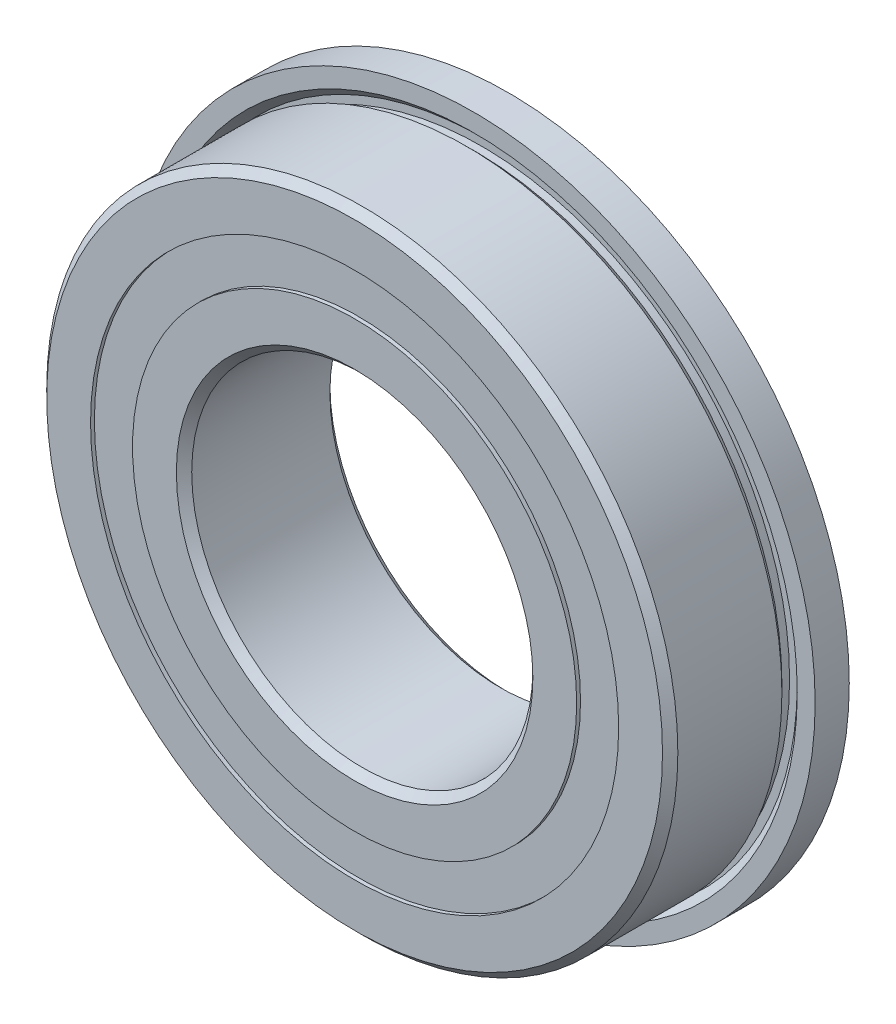
SolidWorks part; units mm, degrees
ref_plane "Front Plane" through (0, 0, 0) normal (0, 0, 1) x (1, 0, 0)
ref_plane "Top Plane" through (0, 0, 0) normal (0, 1, 0) x (1, 0, 0)
ref_plane "Right Plane" through (0, 0, 0) normal (1, 0, 0) x (0, 0, -1)
sketch "Sketch1" plane through (0, 0, 0) normal (0, 0, 1) x (1, 0, 0)
  circle A0 centre (0, 0) radius 10
  dimension "ID" = 20
sketch "Sketch2" plane through (0, 0, 0) normal (1, 0, 0) x (0, 0, -1)
  line L0 (-4.5, 0) -> (4.5, 0) construction
  line L1 (0, 18.5) -> (0, -18.5) construction
  line L2 (4.05, 18.5) -> (-4.05, 18.5) construction
  line L3 (-4.05, 18.5) -> (-4.5, 18.05)
  line L4 (-4.5, 18.05) -> (-4.5, 15.4808)
  line L5 (-4.5, 15.4808) -> (-2, 15.4808)
  line L6 (4.5, 15.4808) -> (2, 15.4808)
  line L7 (4.5, 18.05) -> (4.5, 15.4808)
  line L8 (4.05, 18.5) -> (4.5, 18.05) construction
  line L9 (0, 18.5) -> (0, 14.25) construction
  line L10 (0, 14.25) -> (0, 10) construction
  line L11 (2.5, 0) -> (2.5, 18.5) construction
  line L12 (4.5, 18.05) -> (4.5, 20)
  line L13 (4.5, 20) -> (2.5, 20)
  line L14 (2.5, 20) -> (2.5, 18.95)
  line L15 (2.5, 18.95) -> (2.95, 18.5)
  line L16 (2.95, 18.5) -> (2.95, 18.05)
  line L17 (2.95, 18.05) -> (2.5, 18.05)
  line L18 (2.5, 18.05) -> (2.05, 18.5)
  line L19 (-4.05, 18.5) -> (2.05, 18.5)
  line L20 (4.5, 20) -> (4.5, -20) construction
  line L21 (2.5, 18.5) -> (2.5, 18.95) construction
  line L22 (2.5, 18.5) -> (2.05, 18.5) construction
  line L23 (0, 10) -> (0, -10) construction
  arc A0 (-2, 15.4808) -> (2, 15.4808) centre (0, 14.25) cw
  point P14 (0, 10)
  point P15 (2.5, 0)
  point P25 (4.5, 0)
  point P29 (-4.05, -18.5)
  dimension "D1" = 45
  dimension "D2" = 0.45
  dimension "D3" = 4
  dimension "D4" = 1.2308
  dimension "Flange Thickness" = 2
  dimension "Flange OD" = 40
  dimension "Width" = 9
  dimension "OD" = 37
sketch "Sketch7" plane through (0, 0, 0) normal (1, 0, 0) x (0, 0, -1)
  line L13 (4.5, 20) -> (2.5, 20)
  line L14 (2.5, 20) -> (2.5, 18.95)
  line L15 (2.5, 18.95) -> (2.95, 18.5)
  line L16 (2.95, 18.5) -> (2.95, 18.05)
  line L17 (2.95, 18.05) -> (2.5, 18.05)
  line L18 (2.5, 18.05) -> (2.05, 18.5)
  line L19 (2.05, 18.5) -> (-4.05, 18.5)
  line L20 (-4.05, 18.5) -> (-4.5, 18.05)
  line L21 (-4.5, 18.05) -> (-4.5, 15.4808)
  line L22 (-4.5, 15.4808) -> (-2, 15.4808)
  line L23 (2, 15.4808) -> (4.5, 15.4808)
  line L24 (4.5, 15.4808) -> (4.5, 18.05)
  line L25 (4.5, 18.05) -> (4.5, 20)
  line L26 (4.5, 20) -> (2.5, 20)
  line L27 (2.5, 20) -> (2.5, 18.95)
  line L28 (2.5, 18.95) -> (2.95, 18.5)
  line L29 (2.95, 18.5) -> (2.95, 18.05)
  line L30 (2.95, 18.05) -> (2.5, 18.05)
  line L31 (2.5, 18.05) -> (2.05, 18.5)
  line L32 (2.05, 18.5) -> (-4.05, 18.5)
  line L33 (-4.05, 18.5) -> (-4.5, 18.05)
  line L34 (-4.5, 18.05) -> (-4.5, 15.4808)
  line L35 (-4.5, 15.4808) -> (-2, 15.4808)
  line L36 (2, 15.4808) -> (4.5, 15.4808)
  line L37 (4.5, 15.4808) -> (4.5, 18.05)
  line L38 (4.5, 18.05) -> (4.5, 20)
  arc A1 (2, 15.4808) -> (-2, 15.4808) centre (0, 14.25) ccw
  arc A2 (2, 15.4808) -> (-2, 15.4808) centre (0, 14.25) ccw
  dimension "D1" = 0
revolve "Revolve7" add sketch "Sketch7" angle 360 about L0
sketch "Sketch3" plane through (0, 0, 0) normal (1, 0, 0) x (0, 0, -1)
  line L0 (-4.5, 13.0192) -> (-2, 13.0192)
  line L1 (0, 18.5) -> (0, -18.5) construction
  line L2 (-4.5, 18.05) -> (-4.5, 15.4808) construction
  line L3 (-4.5, 13.0192) -> (-4.5, 10.45)
  line L4 (-4.05, 18.5) -> (-4.5, 18.05) construction
  line L5 (-4.5, 10.45) -> (-4.05, 10)
  line L6 (-4.05, 10) -> (4.05, 10)
  line L8 (4.05, 10) -> (4.5, 10.45)
  line L10 (4.5, 10.45) -> (4.5, 13.0192)
  line L11 (4.5, 13.0192) -> (2, 13.0192)
  line L13 (4.05, 18.5) -> (4.5, 18.05) construction
  arc A0 (2, 15.4808) -> (-2, 15.4808) centre (0, 14.25) ccw construction
  arc A1 (2, 13.0192) -> (-2, 13.0192) centre (0, 14.25) cw
revolve "Revolve3" add sketch "Sketch3" angle 360 about L0
sketch "Sketch6" plane through (0, 0, 0) normal (1, 0, 0) x (0, 0, -1)
  line L1 (-0.2051, 14.8654) -> (0.2051, 14.8654)
  line L2 (-0.2051, 14.8654) -> (-0.2051, 13.6346)
  line L3 (-0.2051, 13.6346) -> (0.2051, 13.6346)
  line L4 (0.2051, 14.8654) -> (0.2051, 13.6346)
  line L5 (-0.2051, 14.8654) -> (0.2051, 13.6346) construction
  line L6 (-0.2051, 13.6346) -> (0.2051, 14.8654) construction
  point P4 (0, 14.25)
  dimension "D1" = 1.2308
  dimension "D2" = 0.4103
revolve "Revolve6" add sketch "Sketch6" angle 360 about L0
sketch "Sketch4" plane through (0, 0, 0) normal (1, 0, 0) x (0, 0, -1)
  line L0 (-2.3484, 14.25) -> (2.3484, 14.25)
  arc A2 (-2.3484, 14.25) -> (2.3484, 14.25) centre (0, 14.25) cw
  arc A3 (2, 15.4808) -> (-2, 15.4808) centre (0, 14.25) ccw construction
revolve "Revolve4" add sketch "Sketch4" angle 360 about L0
ref_axis "Axis1" through (0, 0, -4.5) along (0, 0, 1)
pattern_circular "CirPattern1" count 11 over 360 about axis through (0, 0, -4.5) along (0, 0, 1) of bodies 104
sketch "Sketch5" plane through (0, 0, 0) normal (1, 0, 0) x (0, 0, -1)
  line L0 (-4.5, 15.4808) -> (-2, 15.4808) construction
  line L1 (-4.275, 15.4808) -> (-2.3484, 15.4808)
  line L2 (-4.275, 15.4808) -> (-4.275, 13.0192)
  line L3 (-4.275, 13.0192) -> (-2.3484, 13.0192)
  line L4 (-2.3484, 15.4808) -> (-2.3484, 13.0192)
  line L5 (-4.5, 13.0192) -> (-2, 13.0192) construction
  line L6 (4.5, 15.4808) -> (2, 15.4808) construction
  line L7 (4.275, 15.4808) -> (2.3484, 15.4808)
  line L8 (4.275, 15.4808) -> (4.275, 13.0192)
  line L9 (4.275, 13.0192) -> (2.3484, 13.0192)
  line L10 (2.3484, 15.4808) -> (2.3484, 13.0192)
  line L11 (4.5, 13.0192) -> (2, 13.0192) construction
  line L12 (-4.05, 18.5) -> (-4.5, 18.05) construction
  point P18 (-4.275, 18.275)
revolve "Revolve5" add sketch "Sketch5" angle 360 about L0
equation "\"D2@Sketch2\" = \"Width@Sketch2\" * .05"
equation "\"D3@Sketch2\" = \"Width@Sketch2\" / 2.25"
equation "\"D4@Sketch2\" =  (  (  ( \"OD@Sketch2\" - \"Width@Sketch2\" )  / 2 )  / 3.25 )  / 3.5"
equation "\"D2@CirPattern1\" = 360/\"Balls@CirPattern1\""
equation "\"D1@Sketch6\" = \"D4@Sketch2\""
equation "\"D2@Sketch6\"=\"D1@Sketch6\"/3"
